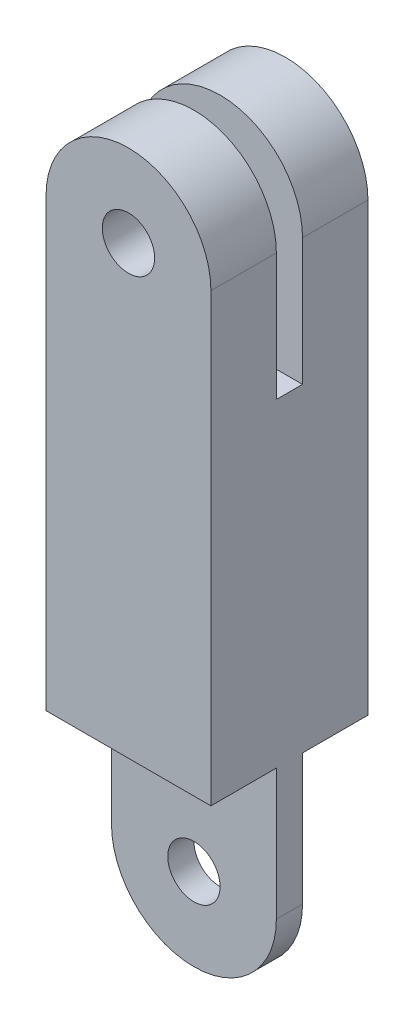
SolidWorks part; units mm, degrees
ref_plane "Front Plane" through (0, 0, 0) normal (0, 0, 1) x (1, 0, 0)
ref_plane "Top Plane" through (0, 0, 0) normal (0, 1, 0) x (1, 0, 0)
ref_plane "Right Plane" through (0, 0, 0) normal (1, 0, 0) x (0, 0, -1)
sketch "Sketch1" plane through (0, 0, 0) normal (0, 0, 1) x (1, 0, 0)
  line L0 (-10, 0) -> (-10, 70)
  line L2 (10, 70) -> (10, 0)
  arc A0 (-10, 0) -> (10, 0) centre (0, 0) ccw
  arc A1 (10, 70) -> (-10, 70) centre (0, 70) ccw
  circle A2 centre (0, 70) radius 3.175
  circle A3 centre (0, 0) radius 3.175
  dimension "D1" = 20
  dimension "D3" = 6.35
  dimension "D2" = 70
extrude "Boss-Extrude1" add sketch "Sketch1" along normal mid plane 19.05
sketch "Sketch2" plane through (0, 0, 0) normal (0, 1, 0) x (1, 0, 0)
  line L0 (10, -9.525) -> (10, 9.525) construction
  line L1 (-10, -9.525) -> (10, -9.525)
  line L2 (-10, -9.525) -> (-10, -1.5875)
  line L3 (-10, -1.5875) -> (10, -1.5875)
  line L4 (10, -9.525) -> (10, -1.5875)
  line L5 (0, 1.5875) -> (0, -1.5875) construction
  line L6 (10, 1.5875) -> (-10, 1.5875)
  line L7 (10, 1.5875) -> (10, 9.525)
  line L8 (10, 9.525) -> (-10, 9.525)
  line L9 (-10, 1.5875) -> (-10, 9.525)
  dimension "D1" = 3.175
extrude "Cut-Extrude1" cut sketch "Sketch2" against normal up to next and the other way blind 15.875
ref_plane "Plane1" through (0, 80, 0) normal (0, 1, 0) x (-1, 0, 0)
sketch "Sketch3" plane through (0, 80, 0) normal (0, 1, 0) x (-1, 0, 0)
  line L0 (-10, 9.525) -> (-10, -9.525) construction
  line L1 (-10, 1.5875) -> (10, 1.5875)
  line L2 (-10, 1.5875) -> (-10, -1.5875)
  line L3 (-10, -1.5875) -> (10, -1.5875)
  line L4 (10, 1.5875) -> (10, -1.5875)
  line L5 (10, 9.525) -> (10, -9.525) construction
  line L6 (-10, 1.5875) -> (10, -1.5875) construction
  dimension "D1" = 3.175
extrude "Cut-Extrude2" cut sketch "Sketch3" against normal blind 25.4
